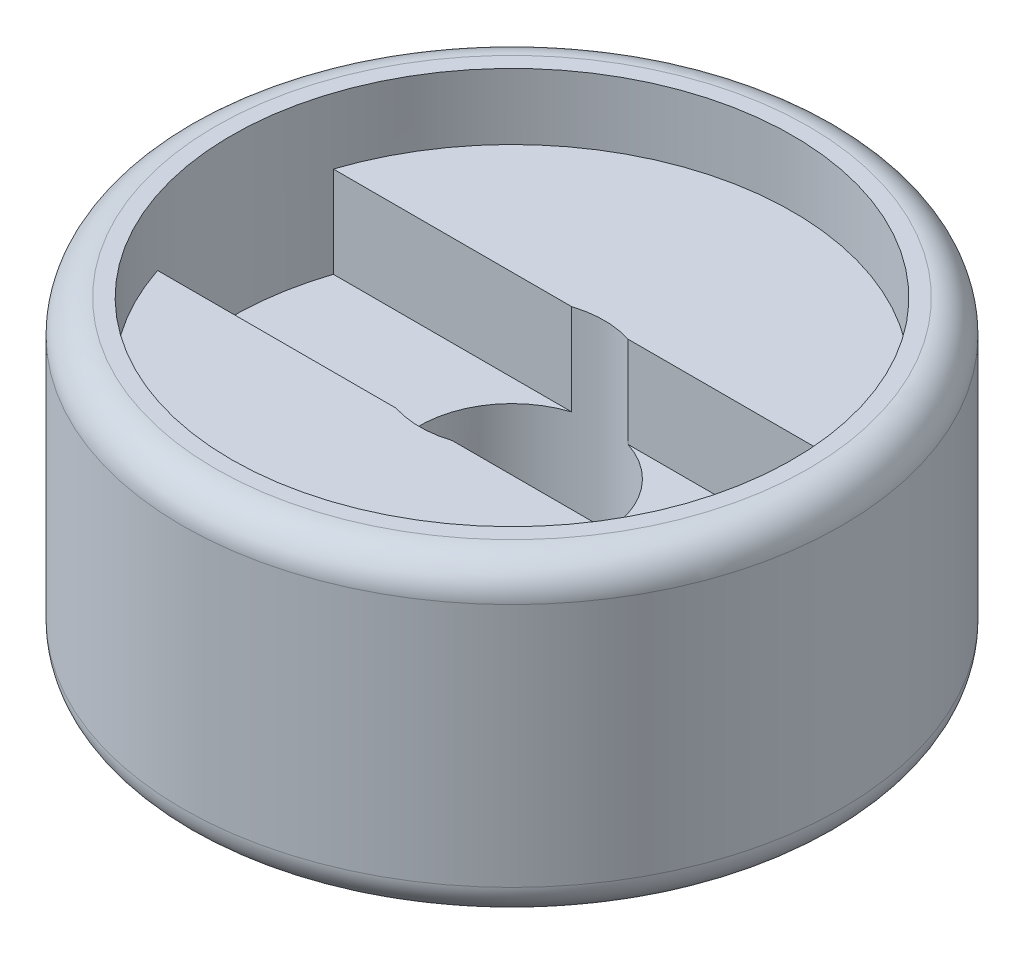
SolidWorks part; units mm, degrees
note: The reader was unsure of these and kept them because the rebuilt part matched: shared geometry of "Sketch1<5>".
ref_plane "Front Plane" through (0, 0, 0) normal (0, 0, 1) x (1, 0, 0)
ref_plane "Top Plane" through (0, 0, 0) normal (0, 1, 0) x (1, 0, 0)
ref_plane "Right Plane" through (0, 0, 0) normal (1, 0, 0) x (0, 0, -1)
sketch "Sketch1" plane through (0, 0, 0) normal (0, 1, 0) x (1, 0, 0)
  line L2 (0, -15) -> (0, -9.5) construction
  circle A1 centre (0, 0) radius 15
  circle A3 centre (0, -9.5) radius 2.1
  circle A4 centre (-8.2272, 4.75) radius 2.1
  circle A5 centre (8.2272, 4.75) radius 2.1
  point P19 (0, 0)
  dimension "D2" = 30
  dimension "D6" = 4.2
  dimension "D4" = 9.5
  dimension "D7" = 3
extrude "Boss-Extrude1" add sketch "Sketch1" along normal blind 7
sketch "Sketch2" plane through (0, 0, 0) normal (0, 1, 0) x (1, 0, 0)
  circle A0 centre (0, 0) radius 4.2
  dimension "D1" = 8.4
extrude "Cut-Extrude1" cut sketch "Sketch2" along normal up to surface (7 mm away) up to face at (0, 7, 15)
sketch "Sketch5" plane through (0, 7, 0) normal (0, 1, 0) x (1, 0, 0)
  line L1 (-14.4568, 4) -> (14.4568, 4)
  line L3 (-14.4568, -4) -> (14.4568, -4)
  line L5 (-14.4568, 4) -> (14.4568, -4) construction
  line L6 (-14.4568, -4) -> (14.4568, 4) construction
  arc A0 (-14.4568, -4) -> (14.4568, -4) centre (0, 0) ccw
  circle A1 centre (0, 0) radius 15 construction
  arc A2 (14.4568, 4) -> (-14.4568, 4) centre (0, 0) ccw
  dimension "D1" = 8
extrude "Boss-Extrude2" add sketch "Sketch5" along normal blind 4.15
extrude "Cut-Extrude2" cut sketch "Sketch1<5>" along normal blind 6.5
sketch "Sketch1<5>" plane through (0, 0, 0) normal (0, 1, 0) x (1, 0, 0) same geometry as "Sketch1"
sketch "Sketch6" plane through (0, 11.15, 0) normal (0, 1, 0) x (1, 0, 0)
  circle A0 centre (0, 0) radius 12.775
  circle A1 centre (0, 0) radius 15
  arc A2 (14.4568, 4) -> (-14.4568, 4) centre (0, 0) ccw construction
  dimension "D1" = 25.55
extrude "Boss-Extrude3" add sketch "Sketch6" along normal blind 3 and the other way up to surface other way up to face at (-8.7344, 7, 0)
fillet "Fillet1" radius 1.5 2 edges at (0, 0, 15) (0, 14.15, 15)
